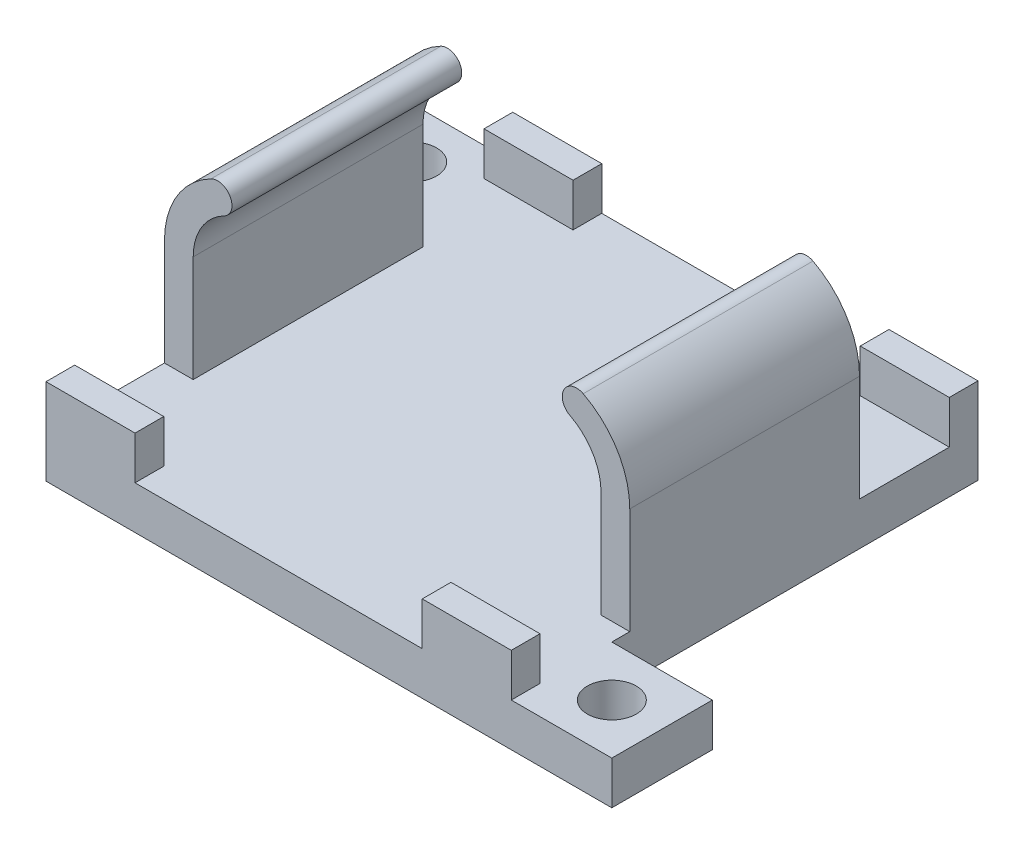
SolidWorks part; units mm, degrees
ref_plane "Front Plane" through (0, 0, 0) normal (0, 0, 1) x (1, 0, 0)
ref_plane "Top Plane" through (0, 0, 0) normal (0, 1, 0) x (1, 0, 0)
ref_plane "Right Plane" through (0, 0, 0) normal (1, 0, 0) x (0, 0, -1)
sketch "Sketch1" plane through (0, 0, 0) normal (0, 0, 1) x (1, 0, 0)
  line L0 (-16.2, -2.2) -> (16.2, -2.2)
  line L1 (-10.2, 8.2) -> (10.2, 8.2)
  line L2 (-16.2, 2.2) -> (-16.2, -8.2)
  line L3 (-16.2, -8.2) -> (16.2, -8.2)
  line L4 (16.2, 2.2) -> (16.2, -8.2)
  line L5 (-16.2, 8.2) -> (16.2, -8.2) construction
  line L6 (-16.2, -8.2) -> (16.2, 8.2) construction
  line L7 (-10.2, 6.2) -> (10.2, 6.2)
  line L8 (-14.2, 2.2) -> (-14.2, -5.2)
  line L9 (-14.2, -5.2) -> (14.2, -5.2)
  line L10 (14.2, 2.2) -> (14.2, -5.2)
  line L11 (-16.2, -5.2) -> (16.2, -5.2)
  line L17 (-10, 4) -> (10, 4)
  line L18 (-10, 4) -> (-10, -5.2)
  line L19 (-10, -5.2) -> (10, -5.2)
  line L20 (10, 4) -> (10, -5.2)
  arc A0 (14.2, 2.2) -> (10.2, 6.2) centre (10.2, 2.2) ccw
  arc A1 (-14.2, 2.2) -> (-10.2, 6.2) centre (-10.2, 2.2) cw
  arc A2 (16.2, 2.2) -> (10.2, 8.2) centre (10.2, 2.2) ccw
  arc A3 (-16.2, 2.2) -> (-10.2, 8.2) centre (-10.2, 2.2) cw
  circle A4 centre (-12.5, 6.6396) radius 1
  circle A5 centre (12.5, 6.6396) radius 1
  point P0 (0, 0)
  point P10 (0, -5.2)
  point P15 (-14.2, 6.2)
  point P30 (0, 0)
  point P35 (0, 4)
  dimension "D5" = 4
  dimension "D6" = 6
  dimension "D9" = 12.5
  dimension "D1" = 11.4
  dimension "D2" = 3
  dimension "D3" = 2
  dimension "D4" = 28.4
  dimension "D7" = 2
  dimension "D8" = 12.5
  dimension "D10" = 4
  dimension "D11" = 20
  dimension "D12" = 3
extrude "Boss-Extrude1" add sketch "Sketch1" along normal blind 14.25 and the other way blind 14.25 contours L11 L2 L3 L4 L9 region at (0, -6.7, 0)
extrude "Boss-Extrude2" add sketch "Sketch1<3>" along normal blind 2 from surface contours L11 L2 L3 L4 L9 | L2 L11 L8 L0 | L18 L0 L8 L9 | L0 L20 L9 L10 | L10 L11 L4 L0 region at (-15.2, -3.7, 0) region at (-12.1, -3.7, 0) region at (0, -6.7, 0) region at (12.1, -3.7, 0) region at (15.2, -3.7, 0) starting at face at (0, -6.7, 14.25)
sketch "Sketch1<3>" plane through (0, 0, 0) normal (0, 0, 1) x (1, 0, 0) same geometry as "Sketch1"
extrude "Boss-Extrude3" add sketch "Sketch1<6>" against normal blind 2 from surface contours L2 L11 L8 L0 | L18 L0 L8 L9 | L11 L2 L3 L4 L9 | L0 L20 L9 L10 | L10 L11 L4 L0 region at (-15.2, -3.7, 0) region at (-12.1, -3.7, 0) region at (0, -6.7, 0) region at (12.1, -3.7, 0) region at (15.2, -3.7, 0) starting at face at (0, -6.7, -14.25)
sketch "Sketch1<6>" plane through (0, 0, 0) normal (0, 0, 1) x (1, 0, 0) same geometry as "Sketch1"
extrude "Boss-Extrude4" add sketch "Sketch1<7>" along normal blind 8 and the other way blind 8 contours L2 L11 L8 L0 | A4 A3 L2 L0 L8 A1 | A4 | A5 | A5 A0 L10 L0 L4 A2 | L10 L11 L4 L0 region at (-14.8694, 2.2734, 0) region at (-15.2, -3.7, 0) region at (-12.5, 6.6396, 0) region at (14.8694, 2.2734, 0) region at (15.2, -3.7, 0) region at (12.5, 6.6396, 0)
sketch "Sketch1<7>" plane through (0, 0, 0) normal (0, 0, 1) x (1, 0, 0) same geometry as "Sketch1"
sketch "Sketch2" plane through (0, 0, 0) normal (0, 1, 0) x (1, 0, 0)
  line L0 (16.2, -8) -> (16.2, -14.25) construction
  line L1 (-23.2, 16.25) -> (-16.2, 16.25)
  line L2 (-23.2, 16.25) -> (-23.2, 9.25)
  line L3 (-23.2, 9.25) -> (-16.2, 9.25)
  line L4 (-16.2, 16.25) -> (-16.2, 9.25)
  line L5 (16.2, -9.25) -> (23.2, -9.25)
  line L6 (16.2, -9.25) -> (16.2, -16.25)
  line L7 (16.2, -16.25) -> (23.2, -16.25)
  line L8 (23.2, -9.25) -> (23.2, -16.25)
  line L9 (-16.2, 14.25) -> (-16.2, 8) construction
  line L10 (10, -16.25) -> (-10, -16.25) construction
  line L11 (-10, 16.25) -> (10, 16.25) construction
  circle A0 centre (-19.7, 12.75) radius 1.7
  circle A1 centre (19.7, -12.75) radius 1.7
  point P12 (0, 0)
  point P13 (23.2, -12.75)
  point P16 (0, 0)
  point P17 (-23.2, 12.75)
  dimension "D7" = 3.4
  dimension "D8" = 3.4
  dimension "D1" = 7
  dimension "D2" = 7
  dimension "D3" = 7
  dimension "D4" = 7
  dimension "D5" = 3.5
  dimension "D6" = 3.5
extrude "Boss-Extrude5" add sketch "Sketch2" along normal blind 3 from surface starting at face at (0, -8.2, 0)
